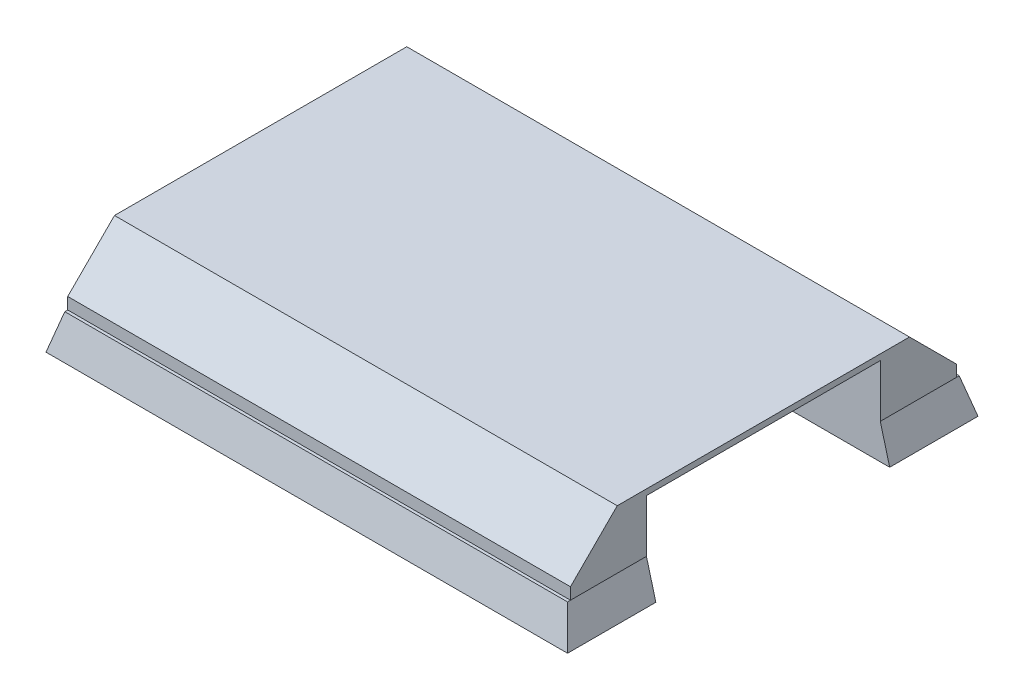
SolidWorks part; units mm, degrees
ref_plane "Спереди" through (0, 0, 0) normal (0, 0, 1) x (1, 0, 0)
ref_plane "Сверху" through (0, 0, 0) normal (0, 1, 0) x (1, 0, 0)
ref_plane "Справа" through (0, 0, 0) normal (1, 0, 0) x (0, 0, -1)
sketch "Эскиз1" plane through (0, 0, 0) normal (0, 1, 0) x (1, 0, 0)
  line L1 (21.5, -16.75) -> (-21.5, -16.75)
  line L2 (21.5, -16.75) -> (21.5, 16.75)
  line L3 (21.5, 16.75) -> (-21.5, 16.75)
  line L4 (-21.5, -16.75) -> (-21.5, 16.75)
  line L5 (21.5, -16.75) -> (-21.5, 16.75) construction
  line L6 (21.5, 16.75) -> (-21.5, -16.75) construction
  point P0 (0, 0)
  dimension "D1" = 33.5
  dimension "D2" = 43
extrude "Бобышка-Вытянуть1" add sketch "Эскиз1" against normal blind 3 draft 15 draft outward yes
sketch "Эскиз2" plane through (0, 0, 0) normal (0, 1, 0) x (1, 0, 0)
  line L1 (-21.5, -16.5) -> (21.5, -16.5)
  line L2 (-21.5, -16.5) -> (-21.5, 16.5)
  line L3 (-21.5, 16.5) -> (21.5, 16.5)
  line L4 (21.5, -16.5) -> (21.5, 16.5)
  line L5 (-21.5, -16.5) -> (21.5, 16.5) construction
  line L6 (-21.5, 16.5) -> (21.5, -16.5) construction
  point P0 (0, 0)
  dimension "D1" = 33
  dimension "D2" = 43
extrude "Бобышка-Вытянуть2" add sketch "Эскиз2" along normal blind 5
sketch "Эскиз3" plane through (21.5, 0, 0) normal (1, 0, 0) x (0, 0, -1)
  line L1 (-10, 3.5) -> (10, 3.5)
  line L2 (-10, 3.5) -> (-10, -3.5)
  line L3 (-10, -3.5) -> (10, -3.5)
  line L4 (10, 3.5) -> (10, -3.5)
  point P4 (0, 0)
  point P7 (-10, -4.008)
  point P8 (0, 0)
  dimension "D1" = 20
  dimension "D2" = 10
  dimension "D3" = 3.5
  dimension "D4" = 7
extrude "Вырез-Вытянуть1" cut sketch "Эскиз3" against normal blind 39
sketch "Эскиз4" plane through (0, 3.5, 0) normal (0, -1, 0) x (1, 0, 0)
  line L0 (21.5, -10) -> (21.5, 10) construction
  line L1 (18.5, 9) -> (10.5, 9)
  line L2 (18.5, 9) -> (18.5, -9)
  line L3 (18.5, -9) -> (10.5, -9)
  line L4 (10.5, 9) -> (10.5, -9)
  line L5 (-17.5, -10) -> (21.5, -10) construction
  dimension "D1" = 8
  dimension "D2" = 3
  dimension "D3" = 18
  dimension "D4" = 1
extrude "Вырез-Вытянуть2" cut sketch "Эскиз4" against normal blind 1
chamfer "Фаска1" distance 1 angle 45 1 edges at (21.5, 3.5, 0)
chamfer "Фаска2" distance 6 angle 45 1 edges at (-17.5, -3, 0)
chamfer "Фаска3" distance 4 angle 45 2 edges at (0, 5, -16.5) (0, 5, 16.5)
sketch "Эскиз5" plane through (21.5, 0, 0) normal (-1, 0, 0) x (0, 0, 1)
  line L1 (-10, -3) -> (10, -3)
  line L2 (-10, -3) -> (-10, 0)
  line L3 (-10, 0) -> (10, 0)
  line L4 (10, -3) -> (10, 0)
extrude "Вырез-Вытянуть3" cut sketch "Эскиз5" against normal through all
